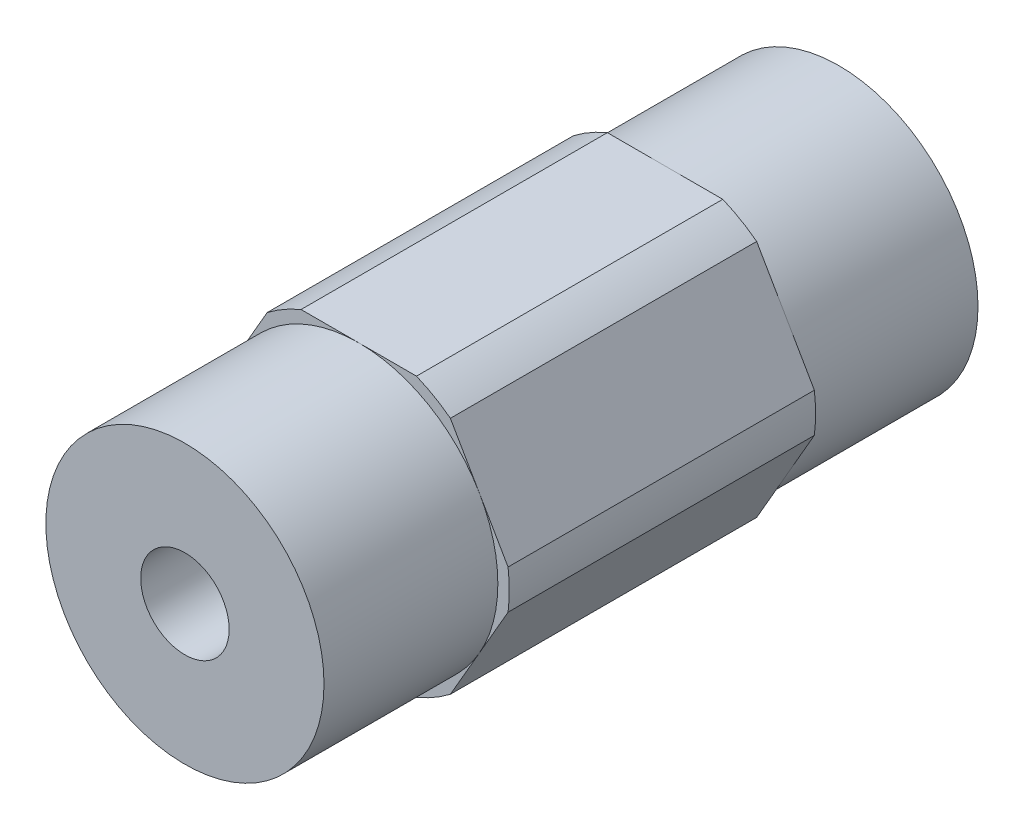
SolidWorks part; units mm, degrees
material "7075-T6 (SN)"
ref_plane "Front Plane" through (0, 0, 0) normal (0, 0, 1) x (1, 0, 0)
ref_plane "Top Plane" through (0, 0, 0) normal (0, 1, 0) x (1, 0, 0)
ref_plane "Right Plane" through (0, 0, 0) normal (1, 0, 0) x (0, 0, -1)
sketch "Sketch1" plane through (0, 0, 0) normal (0, 0, 1) x (1, 0, 0)
  line L1 (7.3323, 0) -> (3.6662, 6.35)
  line L2 (3.6662, 6.35) -> (-3.6662, 6.35)
  line L3 (-3.6662, 6.35) -> (-7.3323, 0)
  line L4 (-7.3323, 0) -> (-3.6662, -6.35)
  line L5 (-3.6662, -6.35) -> (3.6662, -6.35)
  line L6 (3.6662, -6.35) -> (7.3323, 0)
  circle A0 centre (0, 0) radius 6.35 construction
  circle A1 centre (0, 0) radius 2.0193
  circle A2 centre (0, 0) radius 6.875
  dimension "D1" = 12.7
  dimension "D2" = 4.0386
  dimension "D3" = 13.75
extrude "Boss-Extrude1" add sketch "Sketch1" along normal mid plane 29.8602 contours L1 A2 L2 L3 L4 L5 L6 A1 region at (6.6736, 0.4353, 0)
hole_wizard "#10-32 Tapped Hole1" positions "3DSketch1" profile "Sketch3" tap size "#10-32" standard "ANSI Inch"
sketch3d "3DSketch1"
  circle A0 centre (0, 0, -14.9301) radius 2.0193 construction
  circle A1 centre (0, 0, 14.9301) radius 2.0193 construction
  point P0 (0, 0, 14.9301)
  point P2 (0, 0, -14.9301)
  point P6 (0, 0, -12.9108)
  point P9 (0, 0, 16.9494)
sketch "Sketch3" plane through (0, 0, 14.9301) normal (1, 0, 0) x (0, -1, 0)
  line L0 (0, 0) -> (0, 13.1513)
  line L1 (0, 13.1513) -> (2.0193, 11.938)
  line L2 (2.0193, 11.938) -> (2.0193, 0)
  line L5 (2.0193, 0) -> (0, 0)
  line L10 (0, 13.1513) -> (-2.0193, 11.938) construction
  line L11 (0, -6.35) -> (0, 107.95) construction
  dimension "Tap Drill Dia." = 4.0386
  dimension "Tap Drill Depth" = 11.938
  dimension "Drill Angle" = 118
cosmetic thread "Hole Thread1" parameters "D1"=9.652, "D2"=4.826
cosmetic thread "Hole Thread2" parameters "D1"=9.652, "D2"=4.826
sketch "Sketch4" plane through (0, 0, 14.9301) normal (0, 0, 1) x (1, 0, 0)
  circle A0 centre (0, 0) radius 6.35
  dimension "D1" = 12.7
extrude "Cut-Extrude-Thin1" cut sketch "Sketch4" against normal blind 7.9375 thin thin type one direction wall 2.54
mirror "Mirror1" about plane through (0, 0, 0) normal (0, 0, 1) of "Cut-Extrude-Thin1"
equation "\"D3@Sketch1\"=13.75mm"
